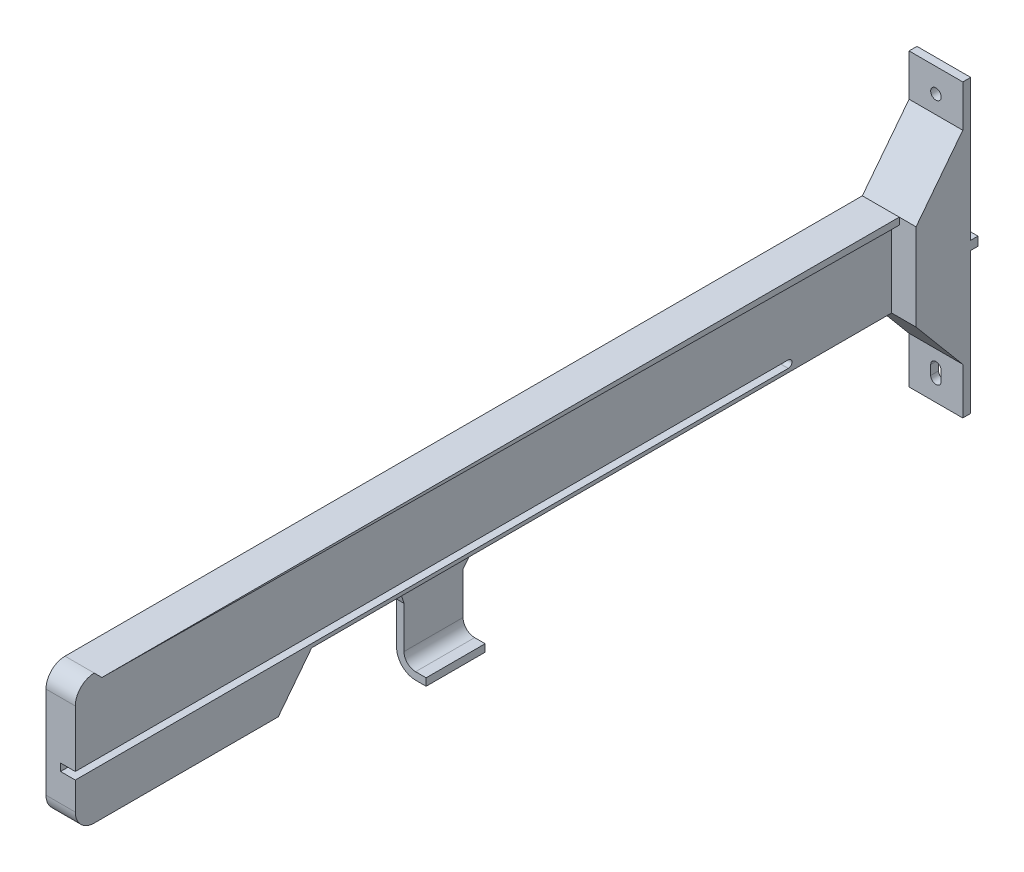
SolidWorks part; units mm, degrees
note: The reader was unsure of these and kept them because the rebuilt part matched: shared geometry of "Sketch1<3>", "Sketch1<4>", "Sketch1<5>".
ref_plane "Front Plane" through (0, 0, 0) normal (0, 0, 1) x (1, 0, 0)
ref_plane "Top Plane" through (0, 0, 0) normal (0, 1, 0) x (1, 0, 0)
ref_plane "Right Plane" through (0, 0, 0) normal (1, 0, 0) x (0, 0, -1)
sketch "Sketch1" plane through (0, 0, 0) normal (1, 0, 0) x (0, 0, -1)
  line L0 (199.075, 43.925) -> (199.075, -81.275)
  line L1 (199.075, -81.275) -> (195.675, -81.275)
  line L2 (195.675, -81.275) -> (195.675, -61.275)
  line L3 (195.675, -61.275) -> (175.575, -37.35)
  line L4 (175.575, -37.35) -> (10.475, -37.35)
  line L5 (10.475, -37.35) -> (0.6285, -50.05)
  line L6 (0.6285, -50.05) -> (0.6285, -76.2)
  line L7 (0.6285, -76.2) -> (-24.7715, -76.2)
  line L8 (-24.7715, -76.2) -> (-24.7715, -50.05)
  line L9 (-24.7715, -50.05) -> (-28.6864, -37.35)
  line L10 (-28.6864, -37.35) -> (-73.9049, -37.35)
  line L11 (-73.9049, -37.35) -> (-88.2715, -55.88)
  line L12 (-88.2715, -55.88) -> (-175.575, -55.88)
  line L13 (-175.575, -55.88) -> (-175.575, 0)
  line L14 (-175.575, 0) -> (175.575, 0)
  line L17 (195.675, 43.925) -> (199.075, 43.925)
  line L18 (175.575, 0) -> (195.675, 25.925)
  line L19 (195.675, 25.925) -> (195.675, 43.925)
  line L20 (175.575, 0) -> (175.575, -37.35)
  line L21 (-28.6864, -37.35) -> (10.475, -37.35)
  line L22 (-24.7715, -73.025) -> (0.6285, -73.025)
  line L23 (175.575, 0) -> (175.575, -37.35) construction
  point P20 (-12.0715, -76.2)
  point P22 (175.575, -18.675)
  point P23 (0, 0)
  point P25 (199.075, -18.675)
  dimension "D1" = 374.65
  dimension "D2" = 37.35
  dimension "D3" = 23.5
  dimension "D4" = 3.4
  dimension "D5" = 125.2
  dimension "D6" = 20
  dimension "D7" = 55.88
  dimension "D8" = 76.2
  dimension "D9" = 165.1
  dimension "D10" = 63.5
  dimension "D11" = 25.4
  dimension "D12" = 12.7
  dimension "D13" = 3.175
  dimension "D14" = 18
extrude "Boss-Extrude1" add sketch "Sketch1" against normal blind 12.6 contours L20 L14 L13 L12 L11 L10 L9 L8 L7 L6 L5 L4
extrude "Boss-Extrude2" add sketch "Sketch1<3>" against normal blind 23.1 contours L18 L20 L3 L2 L1 L0 L17 L19
sketch "Sketch1<3>" plane through (0, 0, 0) normal (1, 0, 0) x (0, 0, -1) same geometry as "Sketch1"
extrude "Boss-Extrude3" add sketch "Sketch1<4>" against normal blind 3.175 contours L8 L22 L6 L5 L21 L9
sketch "Sketch1<4>" plane through (0, 0, 0) normal (1, 0, 0) x (0, 0, -1) same geometry as "Sketch1"
extrude "Boss-Extrude4" add sketch "Sketch1<5>" against normal blind 12.7 contours L22 L8 L7 L6
sketch "Sketch1<5>" plane through (0, 0, 0) normal (1, 0, 0) x (0, 0, -1) same geometry as "Sketch1"
fillet "Fillet1" radius 5 1 edges at (-3.175, -73.025, 12.0715)
fillet "Fillet2" radius 8.175 3 edges at (-6.3, 0, 175.575) (-6.3, -55.88, 175.575) (0, -76.2, 12.0715)
sketch "Sketch2" plane through (-12.6, 0, 0) normal (-1, 0, 0) x (0, 0, 1)
  line L0 (-131.125, -34.175) -> (222.402, -34.175) construction
  line L1 (-131.125, -32.5875) -> (222.402, -32.5875)
  line L2 (-131.125, -35.7625) -> (222.402, -35.7625)
  line L3 (-175.575, -37.35) -> (73.9049, -37.35) construction
  line L4 (-175.575, 0) -> (-175.575, -37.35) construction
  arc A0 (-131.125, -32.5875) -> (-131.125, -35.7625) centre (-131.125, -34.175) ccw
  arc A1 (222.402, -35.7625) -> (222.402, -32.5875) centre (222.402, -34.175) ccw
  point P2 (45.6385, -34.175)
  dimension "D1" = 1.5875
  dimension "D2" = 1.5875
  dimension "D3" = 44.45
extrude "Cut-Extrude1" cut sketch "Sketch2" against normal blind 6.35
sketch "Sketch3" plane through (0, 0, -199.075) normal (0, 0, -1) x (-1, 0, 0)
  line L0 (11.55, -72.325) -> (11.55, -68.275) construction
  line L1 (9.3, -72.325) -> (9.3, -68.275)
  line L2 (13.8, -72.325) -> (13.8, -68.275)
  line L3 (23.1, -81.275) -> (0, -81.275) construction
  line L4 (23.1, 43.925) -> (0, 43.925) construction
  line L5 (11.55, 33.65) -> (11.55, 35.925) construction
  line L6 (11.55, -70.3) -> (9.3, -70.3) construction
  line L7 (11.55, 33.65) -> (9.275, 33.65) construction
  arc A0 (9.3, -72.325) -> (13.8, -72.325) centre (11.55, -72.325) ccw
  arc A1 (13.8, -68.275) -> (9.3, -68.275) centre (11.55, -68.275) ccw
  circle A2 centre (11.55, 33.65) radius 2.275
  point P2 (11.55, -70.3)
  point P7 (11.55, -74.575)
  point P8 (11.55, -66.025)
  point P12 (11.55, -81.275)
  point P17 (11.55, 43.925)
  dimension "D4" = 4.55
  dimension "D1" = 4.5
  dimension "D2" = 8.55
  dimension "D3" = 6.7
  dimension "D5" = 8
extrude "Cut-Extrude2" cut sketch "Sketch3" against normal up to next
sketch "Sketch4" plane through (0, 0, -199.075) normal (0, 0, -1) x (-1, 0, 0)
  line L0 (23.1, -18.675) -> (0, -18.675)
  line L1 (23.1, 43.925) -> (23.1, -81.275) construction
  line L2 (0, 43.925) -> (0, -81.275) construction
  line L3 (11.55, -56.9) -> (11.55, 19.55)
  point P9 (11.55, -18.675)
  dimension "D1" = 76.45
extrude "Extrude-Thin1" add sketch "Sketch4" along normal blind 3.15 thin thin type mid plane wall 3.8
ref_plane "Plane1" through (0, -70.3, 0) normal (0, -1, 0) x (1, 0, 0)
sketch "Sketch5" plane through (0, 0, 0) normal (1, 0, 0) x (0, 0, -1)
  line L0 (-88.2715, -55.88) -> (-167.4, -55.88) construction
  circle A0 centre (-106.425, -48.98) radius 2.875
  dimension "D2" = 5.75
  dimension "D1" = 282
  dimension "D3" = 6.9
extrude "Boss-Extrude5" add sketch "Sketch5" along normal blind 6.2 draft 2
mirror "Mirror1" about plane through (0, 0, 0) normal (1, 0, 0) of "Extrude-Thin1", "Cut-Extrude2", "Cut-Extrude1", "Fillet2", "Fillet1", "Boss-Extrude2", "Boss-Extrude4", "Boss-Extrude3", "Boss-Extrude1"
other "SurfaceCut1"
sketch "Sketch6" plane through (0, 0, 0) normal (-1, 0, 0) x (0, 0, 1)
  line L0 (106.425, -18) -> (106.425, -12.25) construction
  line L4 (-175.575, 0) -> (167.4, 0) construction
  circle A0 centre (106.425, -15.125) radius 2.875
  circle A1 centre (106.425, -48.98) radius 2.875 construction
  point P9 (0, 0)
  dimension "D1" = 18
extrude "Boss-Extrude6" add sketch "Sketch6" along normal blind 6.2
sketch "Sketch7" plane through (12.6, 0, 0) normal (1, 0, 0) x (0, 0, -1)
  line L0 (175.575, 0) -> (175.575, -3)
  line L1 (175.575, 0) -> (175.575, -37.35) construction
  line L2 (175.575, -3) -> (-167.4, 0)
  line L3 (-167.4, 0) -> (175.575, 0)
  dimension "D1" = 3
extrude "Boss-Extrude7" add sketch "Sketch7" along normal blind 3.28
